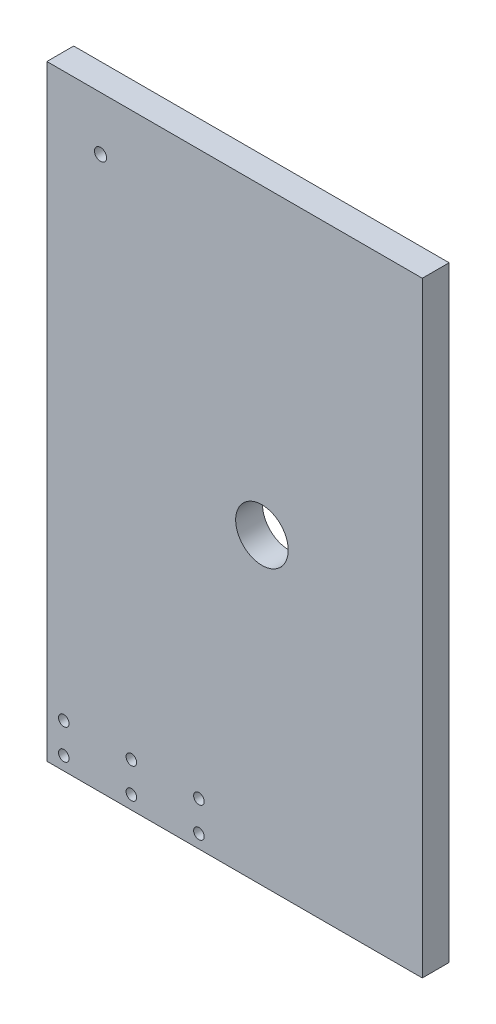
SolidWorks part; units mm, degrees
material "Balsa"
ref_plane "Front Plane" through (0, 0, 0) normal (0, 0, 1) x (1, 0, 0)
ref_plane "Top Plane" through (0, 0, 0) normal (0, 1, 0) x (1, 0, 0)
ref_plane "Right Plane" through (0, 0, 0) normal (1, 0, 0) x (0, 0, -1)
sketch "Sketch1" plane through (0, 0, 0) normal (0, 0, 1) x (1, 0, 0)
  line L0 (-63.5, 59.055) -> (-25.2727, 0.1003) construction
  line L1 (-76.2, 71.755) -> (76.2, 71.755)
  line L2 (-76.2, 71.755) -> (-76.2, -71.755)
  line L3 (-76.2, -71.755) -> (76.2, -71.755)
  line L4 (76.2, 71.755) -> (76.2, -71.755)
  line L5 (-76.2, 71.755) -> (76.2, -71.755) construction
  line L6 (-76.2, -71.755) -> (76.2, 71.755) construction
  line L7 (-25.2727, 0.1003) -> (-63.5159, 0.1003) construction
  circle A0 centre (-63.5, 59.055) radius 1.4375
  circle A1 centre (-25.2727, 0.1003) radius 6.223
  point P0 (0, 0)
  dimension "D1" = 12.446
  dimension "D2" = 70.2637
  dimension "D4" = 2.875
  dimension "D3" = 57.04
  dimension "D5" = 152.4
  dimension "D6" = 71.6547
  dimension "D7" = 12.7
  dimension "D8" = 12.7
  dimension "D9" = 143.51
extrude "Boss-Extrude1" add sketch "Sketch1" along normal blind 6.35 contours L4 L1 L2 L3 A1 A0 region at (0.1604, -0.0182, 0)
sketch "Sketch2" plane through (0, 0, 6.35) normal (0, 0, 1) x (1, 0, 0)
  line L1 (76.2, 71.755) -> (76.2, -71.755) construction
  line L2 (-66.0896, -64.5997) -> (90.0227, -64.5997) construction
  circle A0 centre (63.5, 11.6003) radius 76.2 construction
  circle A1 centre (63.5, 11.6003) radius 3.1115
  circle A2 centre (-25.2727, 0.1003) radius 6.223 construction
  dimension "D1" = 152.4
  dimension "D4" = 64.7
  dimension "D2" = 6.223
  dimension "D3" = 12.7
extrude "Cut-Extrude1" cut sketch "Sketch2" against normal through all contours A1
sketch "Sketch3" plane through (0, 0, 6.35) normal (0, 0, 1) x (1, 0, 0)
  circle A0 centre (-25.2727, 0.1003) radius 18.75 construction
  circle A1 centre (9.6146, -13.6519) radius 18.75 construction
  dimension "D1" = 37.5
sketch "Sketch4" plane through (0, 0, 6.35) normal (0, 0, 1) x (1, 0, 0)
  circle A0 centre (43.8491, -5.2749) radius 1.625
  circle A1 centre (43.8491, -21.2749) radius 1.625
  circle A2 centre (43.8491, -37.2749) radius 1.625
  circle A3 centre (43.8491, 10.7251) radius 1.625
  arc A4 (43.8491, 9.4751) -> (43.8491, 11.9751) centre (43.8491, 10.7251) ccw construction
  arc A5 (43.8491, -6.5249) -> (43.8491, -4.0249) centre (43.8491, -5.2749) ccw construction
  arc A6 (43.8491, -20.0249) -> (43.8491, -22.5249) centre (43.8491, -21.2749) ccw construction
  arc A7 (43.8491, -36.0249) -> (43.8491, -38.5249) centre (43.8491, -37.2749) ccw construction
  dimension "D1" = 3.25
extrude "Cut-Extrude2" cut sketch "Sketch4" against normal through all contours A0 | A1 | A2 | A3 region at (43.8491, -5.2749, 6.35) region at (43.8491, -21.2749, 6.35) region at (43.8491, -37.2749, 6.35)
sketch "Sketch5" plane through (0, 0, 0) normal (0, 0, -1) x (-1, 0, 0)
  line L0 (76.2, -71.755) -> (-76.2, -71.755) construction
  line L1 (-76.2, 71.755) -> (-12.7, 71.755)
  line L2 (-76.2, 71.755) -> (-76.2, -71.755)
  line L3 (-76.2, -71.755) -> (-12.7, -71.755)
  line L4 (-12.7, 71.755) -> (-12.7, -71.755)
  dimension "D1" = 63.5
extrude "Cut-Extrude3" cut sketch "Sketch5" against normal through all
sketch "Sketch6" plane through (0, 0, 0) normal (0, 0, -1) x (-1, 0, 0)
  line L0 (40.2, -65.405) -> (76.2, -65.405) construction
  line L1 (76.2, -71.755) -> (40.2, -71.755) construction
  line L2 (76.2, -71.755) -> (76.2, -61.405) construction
  line L3 (76.2, -61.405) -> (40.2, -61.405) construction
  line L4 (40.2, -71.755) -> (40.2, -61.405) construction
  line L5 (56.2, -61.405) -> (56.2, -65.405) construction
  line L6 (72.2, -61.405) -> (72.2, -65.405) construction
  line L7 (40.2, -68.58) -> (72.2, -68.58) construction
  line L8 (56.2, -65.405) -> (56.2, -71.755) construction
  line L9 (72.2, -65.405) -> (72.2, -68.58) construction
  circle A0 centre (72.2, -61.405) radius 1.25
  circle A1 centre (56.2, -61.405) radius 1.25
  circle A2 centre (40.2, -61.405) radius 1.25
  circle A3 centre (72.2, -68.58) radius 1.25
  circle A4 centre (56.2, -68.58) radius 1.25
  circle A5 centre (40.2, -68.58) radius 1.25
  point P12 (56.2, -68.58)
  point P13 (40.2, -65.405)
  dimension "D5" = 2.5
  dimension "D1" = 10.35
  dimension "D2" = 4
  dimension "D3" = 16
  dimension "D4" = 16
  dimension "D6" = 6.35
extrude "Cut-Extrude4" cut sketch "Sketch6" against normal through all
